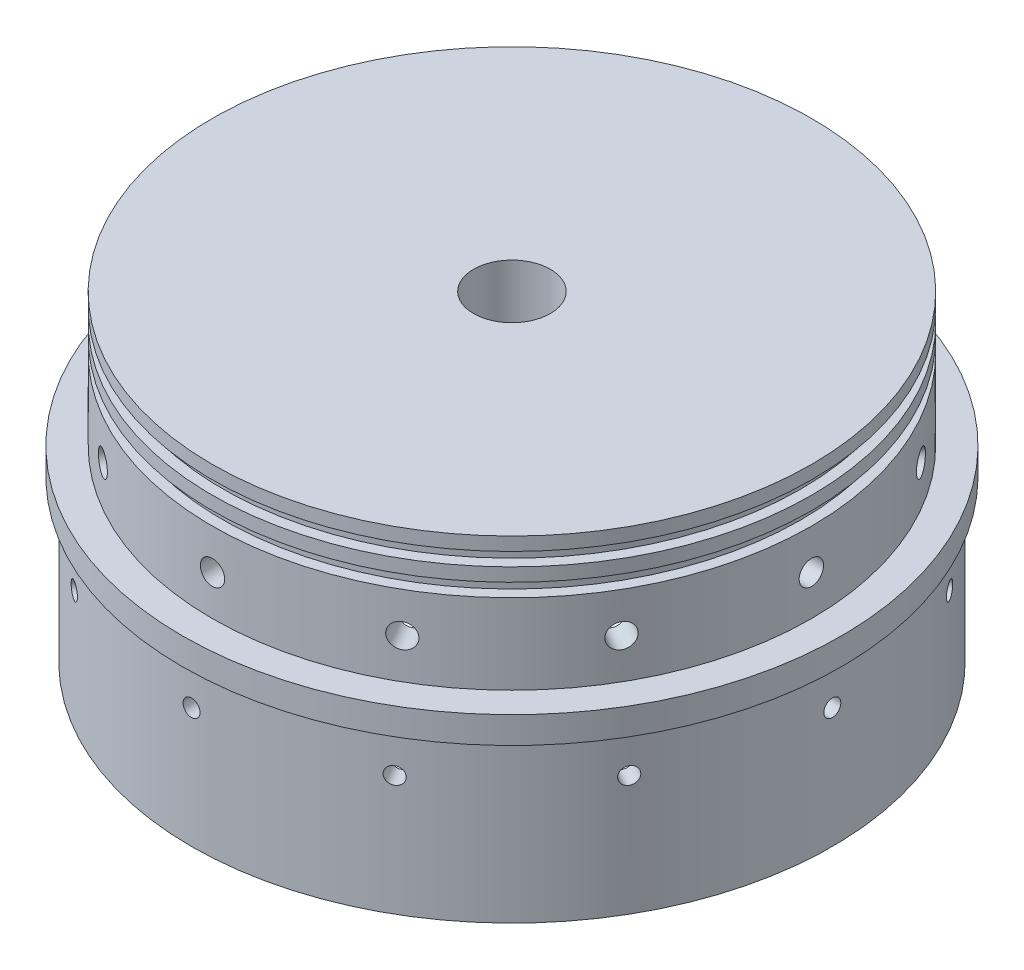
SolidWorks part; units mm, degrees
material "2024-T4"
ref_plane "Front Plane" through (0, 0, 0) normal (0, 0, 1) x (1, 0, 0)
ref_plane "Top Plane" through (0, 0, 0) normal (0, 1, 0) x (1, 0, 0)
ref_plane "Right Plane" through (0, 0, 0) normal (1, 0, 0) x (0, 0, -1)
sketch "Sketch1" plane through (0, 0, 0) normal (0, 1, 0) x (1, 0, 0)
  circle A0 centre (0, 0) radius 78.359
  dimension "D1" = 156.718
extrude "CenterRing(TotOD&Thk)" add sketch "Sketch1" along normal blind 6.35 contours A0 region at (0, 0, 0)
sketch "Sketch2" plane through (0, 6.35, 0) normal (0, 1, 0) x (1, 0, 0)
  circle A0 centre (0, 0) radius 71.247
  dimension "D1" = 142.494
extrude "TankRing(TankID&Ht)" add sketch "Sketch2" along normal blind 31.75
sketch "Sketch3" plane through (0, 0, 0) normal (0, -1, 0) x (1, 0, 0)
  circle A0 centre (0, 0) radius 76.2
  dimension "D1" = 152.4
extrude "FbrGlsRing(FbrGlsID&Ht)" add sketch "Sketch3" along normal blind 38.1
sketch "Sketch4" plane through (0, -38.1, 0) normal (0, -1, 0) x (1, 0, 0)
  circle A0 centre (0, 0) radius 65.0875
  circle A1 centre (0, 0) radius 76.2 construction
  circle A2 centre (0, 0) radius 76.2
  dimension "D1" = 130.175
extrude "Wall&BlkhdThk" cut sketch "Sketch4" against normal offset from surface (60.325 mm away) 15.875 contours A0 up to face at (0, 38.1, 71.247)
sketch "Sketch5" plane through (0, 0, 0) normal (0, 0, 1) x (1, 0, 0)
  line L0 (71.247, 38.1) -> (-71.247, 38.1) construction
  line L1 (-71.247, 38.1) -> (-71.247, 6.35) construction
  line L2 (-71.247, 38.1) -> (-71.247, 6.35)
  line L3 (71.247, 38.1) -> (-71.247, 38.1)
  line L4 (-71.247, 34.925) -> (-68.707, 34.925)
  line L5 (-68.707, 34.925) -> (-68.707, 31.75)
  line L6 (-68.707, 31.75) -> (-71.247, 31.75)
  line L7 (-71.247, 28.575) -> (-68.707, 28.575)
  line L8 (-68.707, 28.575) -> (-68.707, 25.4)
  line L9 (-68.707, 25.4) -> (-71.247, 25.4)
  line L10 (0, 6.35) -> (0, 38.1) construction
  line L11 (78.359, 6.35) -> (-78.359, 6.35) construction
  dimension "D1" = 2.54
  dimension "D2" = 3.175
  dimension "D3" = 3.175
  dimension "D4" = 3.175
  dimension "D5" = 3.175
revolve "O-Ring Channel" cut sketch "Sketch5" angle 360 about L10 region at (-69.977, 33.3375, 0) region at (-69.977, 26.9875, 0)
sketch "Sketch6" plane through (0, 0, 0) normal (0, 0, 1) x (1, 0, 0)
  line L0 (78.359, 6.35) -> (-78.359, 6.35) construction
  line L1 (78.359, 6.35) -> (-78.359, 6.35)
  circle A0 centre (0, 15.875) radius 2.8956
  dimension "D1" = 5.7912
  dimension "D2" = 9.525
extrude "TankBoltHole" cut sketch "Sketch6" against normal through all contours A0 region at (0, 15.875, 0)
pattern_circular "TankBoltCount" count 12 over 360 about axis through (0, 38.1, 0) along (0, -1, 0) of "TankBoltHole"
sketch "Sketch7" plane through (0, 0, 0) normal (0, 0, 1) x (1, 0, 0)
  line L0 (-76.2, 0) -> (76.2, 0) construction
  line L1 (-76.2, 0) -> (76.2, 0)
  circle A0 centre (0, -9.525) radius 2.0193
  dimension "D1" = 4.0386
  dimension "D2" = 9.525
extrude "FbrGlsBoltHole" cut sketch "Sketch7" against normal through all contours A0 region at (0, -9.525, 0)
pattern_circular "FbrGlsBoltCount" count 12 over 360 about axis through (0, -38.1, 0) along (0, 1, 0) of "FbrGlsBoltHole" reverse direction yes
sketch "Sketch8" plane through (0, 38.1, 0) normal (0, 1, 0) x (1, 0, 0)
  circle A0 centre (0, 0) radius 9.1281
  dimension "D1" = 18.2562
extrude "1/2NPTFemDrill" cut sketch "Sketch8" against normal through all
fillet "Smoothing" radius 12.7 1 edges at (0, 22.225, 65.0875)
sketch "Sketch9" plane through (0, -38.1, 0) normal (0, -1, 0) x (1, 0, 0)
  circle A0 centre (0, 0) radius 71.4375
  circle A1 centre (0, 0) radius 76.2 construction
  circle A2 centre (0, 0) radius 76.2
  dimension "D1" = 4.7625
extrude "FbrGlsRingTrim" cut sketch "Sketch9" against normal blind 38.1 contours A0
fillet "TrimSmooting" radius 6.35 1 edges at (0, 0, -71.4375)
equation "\"D4@Sketch5\"=\"D2@Sketch5\""
equation "\"D5@Sketch5\"=\"D3@Sketch5\""
